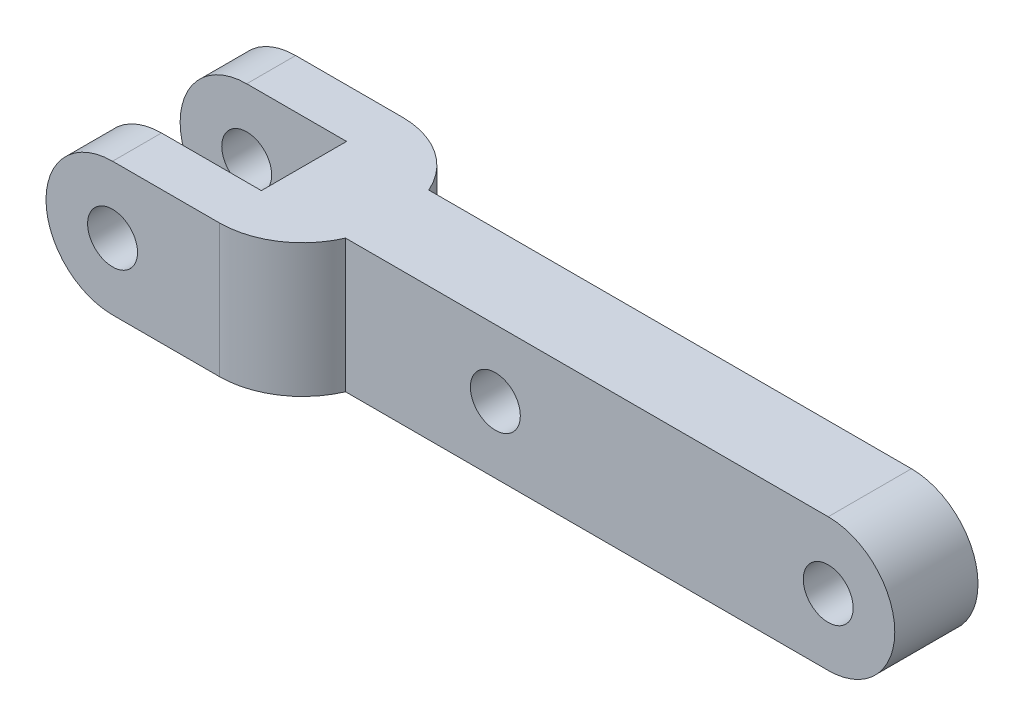
SolidWorks part; units mm, degrees
ref_plane "Front Plane" through (0, 0, 0) normal (0, 0, 1) x (1, 0, 0)
ref_plane "Top Plane" through (0, 0, 0) normal (0, 1, 0) x (1, 0, 0)
ref_plane "Right Plane" through (0, 0, 0) normal (1, 0, 0) x (0, 0, -1)
sketch "Sketch1" plane through (0, 0, 0) normal (0, 0, 1) x (1, 0, 0)
  line L0 (-35.377, 0) -> (-15.377, 0) construction
  line L1 (-35.377, 4) -> (-15.377, 4)
  line L2 (-35.377, -4) -> (-15.377, -4)
  arc A0 (-35.377, 4) -> (-35.377, -4) centre (-35.377, 0) ccw
  arc A1 (-15.377, -4) -> (-15.377, 4) centre (-15.377, 0) ccw
  circle A2 centre (-35.377, 0) radius 1.5
  circle A3 centre (-15.377, 0) radius 1.5
  point P3 (-25.377, 0)
  point P13 (-11.377, 0)
  dimension "D2" = 3
  dimension "D3" = 3
  dimension "D1" = 20
  dimension "D4" = 8
  dimension "D6" = 4
extrude "Boss-Extrude1" add sketch "Sketch1" along normal blind 5
sketch "Sketch3" plane through (0, 0, 5) normal (0, 0, 1) x (1, 0, 0)
  line L0 (-15.377, 0) -> (-55.377, 0) construction
  line L1 (-15.377, -4) -> (-55.377, -4)
  line L2 (-15.377, 4) -> (-55.377, 4)
  arc A0 (-15.377, -4) -> (-15.377, 4) centre (-15.377, 0) ccw
  arc A1 (-55.377, 4) -> (-55.377, -4) centre (-55.377, 0) ccw
  circle A2 centre (-55.377, 0) radius 1.5
  circle A3 centre (-35.377, 0) radius 1.5 construction
  point P4 (-35.377, 0)
  arc M8 (-35.377, 4) -> (-35.377, -4) centre (-35.377, 0) ccw
  dimension "D1" = 8
  dimension "D2" = 40
extrude "Boss-Extrude3" add sketch "Sketch3" against normal blind 5 contours L2 A1 L1 A2 M8 region at (-48.2016, 0, 5)
sketch "Sketch5" plane through (0, 0, 5) normal (0, 0, 1) x (1, 0, 0)
  line L0 (-44.377, 4) -> (-44.377, -4)
  line L1 (-15.377, 4) -> (-55.377, 4) construction
  line L2 (-55.377, -4) -> (-15.377, -4) construction
  line L5 (-15.377, 4) -> (-55.377, 4)
  line L6 (-55.377, -4) -> (-15.377, -4)
  line L7 (-44.377, 4) -> (-55.377, 4)
  line L8 (-55.377, -4) -> (-44.377, -4)
  arc A1 (-55.377, 4) -> (-55.377, -4) centre (-55.377, 0) ccw construction
  arc A4 (-55.377, 4) -> (-55.377, -4) centre (-55.377, 0) ccw
  arc A5 (-15.377, -4) -> (-15.377, 4) centre (-15.377, 0) ccw
  arc A6 (-55.377, 4) -> (-55.377, -4) centre (-55.377, 0) ccw
  point P10 (-59.377, 0)
  line M3 (-15.377, 4) -> (-55.377, 4)
  arc M4 (-55.377, 4) -> (-55.377, -4) centre (-55.377, 0) ccw
  line M5 (-55.377, -4) -> (-15.377, -4)
  circle M8 centre (-55.377, 0) radius 1.5
  dimension "D1" = 15
  dimension "D2" = 0
extrude "Boss-Extrude5" add sketch "Sketch5" against normal blind 5 and the other way blind 6 from offset 3 contours L0 M3 M4 M5 M8 region at (-51.216, 0, 5) offset against normal yes
sketch "Sketch6" plane through (0, 4, 0) normal (0, 1, 0) x (1, 0, 0)
  line L0 (-59.377, 3) -> (-59.377, -8) construction
  line L1 (-59.377, -5.06) -> (-49.377, -5.06)
  line L2 (-59.377, -5.06) -> (-59.377, 0.06)
  line L3 (-59.377, 0.06) -> (-49.377, 0.06)
  line L4 (-49.377, -5.06) -> (-49.377, 0.06)
  line L5 (-55.377, 3) -> (-55.377, -8) construction
  point P6 (-59.377, -2.5)
  point P9 (-55.377, -2.5)
  dimension "D1" = 0
  dimension "D2" = 5.12
  dimension "D3" = 10
extrude "Cut-Extrude1" cut sketch "Sketch6" against normal blind 10
fillet "Fillet1" radius 5 2 edges at (-44.377, 0, -3) (-44.377, 0, 8)
